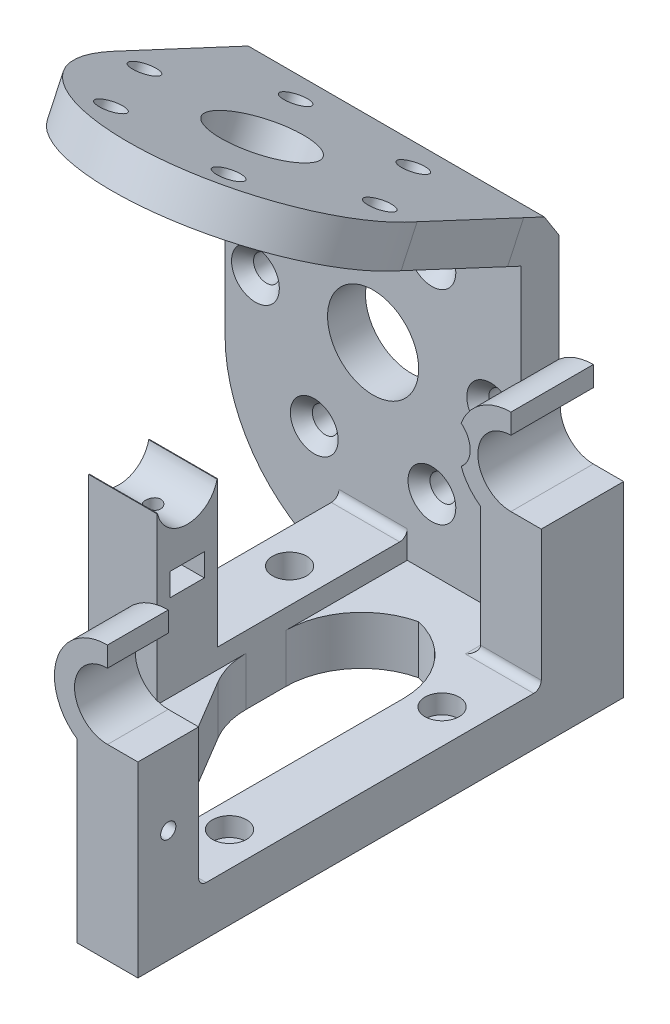
SolidWorks part; units mm, degrees
ref_plane "Front Plane" through (0, 0, 0) normal (0, 0, 1) x (1, 0, 0)
ref_plane "Top Plane" through (0, 0, 0) normal (0, 1, 0) x (1, 0, 0)
ref_plane "Right Plane" through (0, 0, 0) normal (1, 0, 0) x (0, 0, -1)
sketch "Sketch5" plane through (0, 0, 0) normal (0, 0, 1) x (1, 0, 0)
  line L0 (0, 0) -> (0, 15.5) construction
  circle A0 centre (0, 0) radius 19.5
  circle A1 centre (-7.75, 13.4234) radius 1.5
  circle A2 centre (0, 0) radius 6
  circle A3 centre (7.75, 13.4234) radius 1.5
  circle A4 centre (15.5, 0) radius 1.5
  circle A5 centre (7.75, -13.4234) radius 1.5
  circle A6 centre (-7.75, -13.4234) radius 1.5
  circle A7 centre (-15.5, 0) radius 1.5
  point P18 (0, 0)
  dimension "D2" = 3
  dimension "D3" = 39
  dimension "D4" = 12
  dimension "D1" = 15.5
  dimension "D5" = 6
extrude "Boss-Extrude1" add sketch "Sketch5" along normal blind 5
hole_wizard "CSK for M3 Flat Head Machine Screw1" positions "Sketch7" profile "Sketch6" countersink size "M3" standard "ANSI Metric" end condition through all
sketch "Sketch7" plane through (0, 0, 5) normal (0, 0, 1) x (1, 0, 0)
  point P0 (-15.5, 0)
  point P3 (-7.75, 13.4234)
  point P6 (7.75, 13.4234)
  point P9 (15.5, 0)
  point P12 (7.75, -13.4234)
  point P15 (-7.75, -13.4234)
sketch "Sketch6" plane through (-15.5, 0, 5) normal (1, 0, 0) x (0, -1, 0)
  line L0 (0, 0) -> (0, 5)
  line L1 (0, 5) -> (1.7, 5)
  line L2 (1.7, 5) -> (1.7, 1.45)
  line L3 (1.7, 1.45) -> (3.15, 0)
  line L5 (3.15, 0) -> (0, 0)
  line L6 (-1.7, 1.45) -> (-3.15, 0) construction
  line L11 (0, -6.35) -> (0, 107.95) construction
  dimension "Thru Hole Dia." = 3.4
  dimension "Thru Hole Depth" = 5
  dimension "Near C'Sink Dia." = 6.3
  dimension "Near C'Sink Angle" = 90
sketch "Sketch8" plane through (0, 0, 5) normal (0, 0, 1) x (1, 0, 0)
  line L0 (-19.5, 0) -> (-19.5, -25)
  line L1 (-19.5, -25) -> (19.5, -25)
  line L2 (19.5, -25) -> (19.5, 0)
  circle A0 centre (0, 0) radius 19.5 construction
  arc A1 (-19.5, 0) -> (19.5, 0) centre (0, 0) ccw
  dimension "D1" = 25
extrude "Boss-Extrude2" add sketch "Sketch8" against normal up to surface (5 mm away) up to face at (-13.8, 0, 0)
sketch "Sketch9" plane through (0, 0, 5) normal (0, 0, 1) x (1, 0, 0)
  line L0 (-19.5, -25) -> (19.5, -25) construction
  line L4 (-4.5, -20) -> (-4.5, -25)
  line L5 (4.5, -20) -> (-4.5, -25) construction
  line L6 (4.5, -25) -> (-4.5, -20) construction
  line L7 (-19.5, -25) -> (0, -22.5) construction
  line L8 (0, -22.5) -> (19.5, -25) construction
  line L9 (-4.5, -25) -> (4.5, -25)
  line L10 (-4.5, -20) -> (4.5, -20)
  line L11 (4.5, -20) -> (4.5, -25)
  point P0 (0, -22.5)
  dimension "D1" = 5
  dimension "D2" = 9
extrude "Boss-Extrude3" add sketch "Sketch9" along normal blind 32.9817
sketch "Sketch10" plane through (0.3712, -20, 0) normal (0, 1, 0) x (1, 0, 0)
  line L1 (-4.8712, -37.9817) -> (4.1288, -37.9817)
  line L2 (-4.8712, -37.9817) -> (-4.8712, -29.9817)
  line L3 (-4.8712, -29.9817) -> (4.1288, -29.9817)
  line L4 (4.1288, -37.9817) -> (4.1288, -29.9817)
  line L6 (-4.8712, -37.9817) -> (-4.8712, -5) construction
  line L7 (4.1288, -37.9817) -> (4.1288, -5) construction
  dimension "D1" = 8
extrude "Boss-Extrude4" add sketch "Sketch10" along normal blind 24
sketch "Sketch11" plane through (-4.5, 0, 0) normal (-1, 0, 0) x (0, 0, 1)
  line L0 (29.9817, 4) -> (29.9817, -20) construction
  line L2 (29.9817, 4) -> (37.9817, 4) construction
  line L3 (37.9817, 4) -> (37.9817, -25) construction
  line L4 (29.9817, 0) -> (27.1369, 2.0822)
  line L5 (27.1369, 2.0822) -> (27.3574, 4.8482)
  line L6 (27.3574, 4.8482) -> (32.7492, 5.4696)
  line L7 (32.7492, 5.4696) -> (41.4483, 5.0286)
  line L8 (41.4483, 5.0286) -> (40.8237, 2.383)
  line L9 (40.8237, 2.383) -> (37.9817, 0)
  line L10 (29.9817, -0.8) -> (30.0625, -0.8)
  line L11 (37.9009, -0.8) -> (37.9817, -0.8)
  line L12 (37.9817, 0) -> (37.9817, -0.8)
  line L13 (29.9817, -0.8) -> (29.9817, 0)
  arc A0 (30.0625, -0.8) -> (37.9009, -0.8) centre (33.9817, 0) ccw
  dimension "D1" = 0.8
extrude "Cut-Extrude1" cut sketch "Sketch11" against normal blind 20
sketch "Sketch12" plane through (0, -0.8, 0) normal (0, 1, 0) x (1, 0, 0)
  line L0 (-4.5, -29.9817) -> (4.5, -37.9817) construction
  line L1 (4.5, -29.9817) -> (-4.5, -37.9817) construction
  line L2 (4.5, -37.9009) -> (4.5, -30.0625) construction
  line L3 (4.5, -29.9817) -> (4.5, -5) construction
  circle A0 centre (0, -33.9817) radius 1
  dimension "D1" = 2
extrude "Cut-Extrude2" cut sketch "Sketch12" against normal blind 16
sketch "Sketch13" plane through (-4.5, 0, 0) normal (-1, 0, 0) x (0, 0, 1)
  line L0 (29.9817, -8.9707) -> (31.7317, -8.9707) construction
  line L1 (31.7317, -8.2443) -> (36.2317, -8.2443)
  line L2 (31.7317, -8.2443) -> (31.7317, -11.2443)
  line L3 (31.7317, -11.2443) -> (36.2317, -11.2443)
  line L4 (36.2317, -8.2443) -> (36.2317, -11.2443)
  line L5 (29.9817, -0.8) -> (29.9817, -20) construction
  line L6 (37.9817, -0.8) -> (37.9817, -25) construction
  line L7 (36.2317, -8.9707) -> (37.9817, -8.9707) construction
  dimension "D1" = 4.5
  dimension "D2" = 3
extrude "Cut-Extrude3" cut sketch "Sketch13" against normal up to surface (9 mm away) up to face at (4.5, -12.05, 26.7363)
sketch "Sketch14" plane through (0, -25, 0) normal (0, -1, 0) x (1, 0, 0)
  line L0 (4.5, 37.9817) -> (4.5, 5) construction
  line L1 (4.5, 5) -> (28.015, 5)
  line L2 (4.5, 5) -> (4.5, 11)
  line L3 (4.5, 11) -> (20.015, 11)
  line L4 (28.015, 5) -> (28.015, 12.4921)
  line L5 (28.015, 3.392) -> (28.015, 40.8737) construction
  line L6 (20.015, 100.392) -> (20.015, 53.8737) construction
  line L8 (28.015, 12.4921) -> (28.015, 64)
  line L9 (28.015, 64) -> (20.015, 64)
  line L10 (20.015, 11) -> (20.015, 64)
  line L12 (4.5, 5) -> (19.5, 5) construction
  dimension "D1" = 0
  dimension "D2" = 6
  dimension "D3" = 59
extrude "Boss-Extrude5" add sketch "Sketch14" against normal blind 2.4
sketch "Sketch15" plane through (28.015, 0, 0) normal (1, 0, 0) x (0, 0, -1)
  line L0 (-54.8737, 4) -> (-100.392, 4) construction
  line L1 (-64, -22.6) -> (-56, -22.6)
  line L2 (-64, -22.6) -> (-64, 4)
  line L3 (-64, 4) -> (-56, 4)
  line L4 (-56, -22.6) -> (-56, 4)
  line L6 (-5, -22.6) -> (-13, -22.6)
  line L7 (-5, -22.6) -> (-5, 4)
  line L8 (-5, 4) -> (-13, 4)
  line L9 (-13, -22.6) -> (-13, 4)
  dimension "D1" = 8
extrude "Boss-Extrude6" add sketch "Sketch15" against normal up to surface (8 mm away) up to face at (20.015, -23.8, 37.5)
sketch "Sketch16" plane through (0, 0, 64) normal (0, 0, 1) x (1, 0, 0)
  line L0 (20.015, -1.0579) -> (20.1574, -1.0579)
  line L1 (20.015, 4) -> (20.015, -25) construction
  line L2 (28.015, 4) -> (28.015, -25) construction
  line L3 (28.015, -1.0579) -> (30.9797, 0.9089)
  line L4 (30.9797, 0.9089) -> (30.0419, 7.8056)
  line L5 (20.015, -1.0579) -> (20.015, 9.2476)
  line L6 (20.015, 3) -> (20.015, 15.4952) construction
  line L7 (20.015, 9.2476) -> (30.0419, 7.8056)
  line L8 (27.8726, -1.0579) -> (28.015, -1.0579)
  arc A0 (20.1574, -1.0579) -> (27.8726, -1.0579) centre (24.015, 0) ccw
extrude "Cut-Extrude4" cut sketch "Sketch16" against normal up to surface (59 mm away) up to face at (22.51, -14.5333, 5)
sketch "Sketch17" plane through (0, -22.6, 0) normal (0, 1, 0) x (1, 0, 0)
  line L0 (20.015, -56) -> (20.015, -13) construction
  line L1 (20.015, -13.8581) -> (28.015, -13.8581)
  line L2 (20.015, -13.8581) -> (20.015, -10.8581)
  line L3 (20.015, -10.8581) -> (28.015, -10.8581)
  line L4 (28.015, -13.8581) -> (28.015, -10.8581)
  line L5 (28.015, -5) -> (28.015, -13) construction
  dimension "D1" = 3
extrude "Cut-Extrude5" cut sketch "Sketch17" along normal up to surface (21.5421 mm away) up to face at (20.0862, -1.0579, 9)
sketch "Sketch19" plane through (0, 0, 29.9817) normal (0, 0, -1) x (-1, 0, 0)
  circle A0 centre (-7.75, -13.4234) radius 3
  dimension "D1" = 6
extrude "Cut-Extrude6" [suppressed] cut sketch "Sketch19" against normal through all
sketch "Sketch20" plane through (0, -22.6, 0) normal (0, 1, 0) x (1, 0, 0)
  line L0 (20.015, -64) -> (4.5, -37.9817)
  line L1 (20.015, -55) -> (4.5, -28.9817)
  line L2 (20.015, -56) -> (20.015, -11) construction
  line L3 (4.5, -29.9817) -> (4.5, -5) construction
  line L4 (4.5, -28.9817) -> (4.5, -37.9817)
  line L5 (20.015, -55) -> (20.015, -64)
  dimension "D1" = 9
extrude "Boss-Extrude7" add sketch "Sketch20" against normal up to surface (2.4 mm away) up to face at (8.005, -25, 20.4969)
fillet "Fillet1" radius 10 3 edges at (20.015, -23.8, 11) (4.5, -23.8, 11) (4.5, -23.8, 28.9817)
fillet "Fillet2" radius 1 1 edges at (20.015, -23.8, 55)
fillet "Fillet3" radius 1 4 edges at (0, -20, 5) (20.015, -22.6, 7.9291) (24.015, -22.6, 10.8581) (24.015, -22.6, 56)
sketch "Sketch22" plane through (28.015, 0, 0) normal (1, 0, 0) x (0, 0, -1)
  circle A0 centre (-60, -7.7015) radius 1
extrude "Cut-Extrude7" [suppressed] cut sketch "Sketch22" against normal up to surface (8 mm away) up to face at (20.015, -11.329, 7.9291)
sketch "Sketch23" plane through (28.015, 0, 0) normal (1, 0, 0) x (0, 0, -1)
  circle A0 centre (-7.9291, -7.7015) radius 1
extrude "Cut-Extrude8" [suppressed] cut sketch "Sketch23" against normal up to surface (8 mm away) up to face at (20.015, -11.329, 7.9291)
sketch "Sketch24" plane through (0, 0, 5) normal (0, 0, -1) x (-1, 0, 0)
  line L0 (-20.015, -21.6) -> (-20.015, -1.0579) construction
  line L1 (-28.015, -1.0579) -> (-28.015, -25) construction
  line L4 (-20.015, -5.7446) -> (-20.015, -1.0579)
  line L5 (-28.015, -1.0579) -> (-28.015, -5.7446)
  line L6 (-27.8726, -1.0579) -> (-28.015, -1.0579)
  line L7 (-20.015, -1.0579) -> (-20.1574, -1.0579)
  arc A0 (-20.1574, -1.0579) -> (-27.8726, -1.0579) centre (-24.015, 0) ccw
  arc A1 (-20.015, -5.7446) -> (-17.4629, -2.4637) centre (-24.015, 0) ccw
  circle A2 centre (-15.5, 0) radius 3.15 construction
  arc A3 (-17.4629, 2.4637) -> (-17.4629, -2.4637) centre (-15.5, 0) ccw
  arc A4 (-17.4629, 2.4637) -> (-28.015, -5.7446) centre (-24.015, 0) ccw
  dimension "D1" = 14
extrude "Boss-Extrude8" add sketch "Sketch24" against normal up to surface (5.8581 mm away) up to face at (24.015, -8.3956, 10.8581)
sketch "Sketch25" plane through (0, 0, 64) normal (0, 0, 1) x (1, 0, 0)
  line L0 (20.015, -5.7446) -> (20.015, -1.0579)
  line L1 (20.015, -1.0579) -> (20.1574, -1.0579)
  line L2 (27.8726, -1.0579) -> (28.015, -1.0579)
  line L3 (28.015, -1.0579) -> (28.015, -5.7446)
  circle A0 centre (24.015, 0) radius 4 construction
  arc A2 (27.8726, -1.0579) -> (20.1574, -1.0579) centre (24.015, 0) ccw
  arc A3 (28.015, -5.7446) -> (20.015, -5.7446) centre (24.015, 0) ccw
extrude "Boss-Extrude9" add sketch "Sketch25" against normal up to surface (8 mm away) up to face at (24.015, -8.3956, 56)
sketch "Sketch26" plane through (0, 0, 64) normal (0, 0, 1) x (1, 0, 0)
  circle A0 centre (24.015, 0) radius 4.35
  dimension "D1" = 8.7
extrude "Cut-Extrude9" cut sketch "Sketch26" against normal up to surface (59 mm away) up to face at (22.1195, -11.2362, 5)
sketch "Sketch27" plane through (0, -25, 0) normal (0, -1, 0) x (1, 0, 0)
  line L0 (4.5, 26.2265) -> (4.5, 21) construction
  line L1 (20.015, 51.3705) -> (20.015, 21) construction
  line L2 (18.1561, 51.8827) -> (5.9111, 31.3481) construction
  line L3 (4.5, 26.2265) -> (4.5, 21)
  line L4 (20.015, 51.3705) -> (20.015, 21)
  line L5 (18.1561, 51.8827) -> (5.9111, 31.3481)
  line L10 (19.5, 0) -> (19.5, 5)
  line L11 (19.5, 5) -> (28.015, 5)
  line L12 (28.015, 5) -> (28.015, 64)
  line L13 (28.015, 64) -> (20.015, 64)
  line L14 (20.015, 64) -> (4.5, 37.9817)
  line L15 (4.5, 37.9817) -> (-4.5, 37.9817)
  line L16 (-4.5, 37.9817) -> (-4.5, 5)
  line L17 (-4.5, 5) -> (-19.5, 5)
  line L18 (-19.5, 5) -> (-19.5, 0)
  line L19 (-19.5, 0) -> (19.5, 0)
  line L20 (19.5, 0) -> (19.5, 5)
  line L21 (19.5, 5) -> (28.015, 5)
  line L22 (28.015, 5) -> (28.015, 64)
  line L23 (28.015, 64) -> (20.015, 64)
  line L24 (20.015, 64) -> (4.5, 37.9817)
  line L25 (4.5, 37.9817) -> (-4.5, 37.9817)
  line L26 (-4.5, 37.9817) -> (-4.5, 5)
  line L27 (-4.5, 5) -> (-19.5, 5)
  line L28 (-19.5, 5) -> (-19.5, 0)
  line L29 (-19.5, 0) -> (19.5, 0)
  arc A0 (12.2575, 11.2547) -> (20.015, 21) centre (10.015, 21) ccw construction
  arc A1 (4.5, 21) -> (12.2575, 11.2547) centre (14.5, 21) ccw construction
  arc A2 (5.9111, 31.3481) -> (4.5, 26.2265) centre (14.5, 26.2265) ccw construction
  arc A3 (20.015, 51.3705) -> (18.1561, 51.8827) centre (19.015, 51.3705) ccw construction
  arc A4 (12.2575, 11.2547) -> (20.015, 21) centre (10.015, 21) ccw
  arc A5 (4.5, 21) -> (12.2575, 11.2547) centre (14.5, 21) ccw
  arc A6 (5.9111, 31.3481) -> (4.5, 26.2265) centre (14.5, 26.2265) ccw
  arc A7 (20.015, 51.3705) -> (18.1561, 51.8827) centre (19.015, 51.3705) ccw
  dimension "D1" = 0
extrude "Boss-Extrude10" add sketch "Sketch27" along normal blind 4
sketch "Sketch28" plane through (0, -22.6, 0) normal (0, 1, 0) x (1, 0, 0)
  line L0 (23.515, -11.8581) -> (23.515, -55) construction
  line L3 (23.515, -19.4291) -> (23.515, -33.4291) construction
  line L4 (23.515, -33.4291) -> (23.515, -47.4291) construction
  circle A0 centre (23.515, -19.4291) radius 1
  circle A1 centre (23.515, -47.4291) radius 1
  dimension "D1" = 2
  dimension "D2" = 28
  dimension "D3" = 14
extrude "Cut-Extrude10" cut sketch "Sketch28" against normal through all
sketch "Sketch29" plane through (0, -22.6, 0) normal (0, 1, 0) x (1, 0, 0)
  circle A0 centre (23.515, -19.4291) radius 2.25
  circle A1 centre (23.515, -47.4291) radius 2.25
  dimension "D1" = 4.5
extrude "Cut-Extrude11" cut sketch "Sketch29" against normal blind 2.5
sketch "Sketch30" plane through (0, -20, 0) normal (0, 1, 0) x (1, 0, 0)
  line L0 (4.5, -6) -> (-4.5, -6) construction
  circle A0 centre (0, -16) radius 1
  dimension "D1" = 2
  dimension "D2" = 10
extrude "Cut-Extrude12" cut sketch "Sketch30" against normal through all
sketch "Sketch31" plane through (0, -20, 0) normal (0, 1, 0) x (1, 0, 0)
  circle A0 centre (0, -16) radius 2.25
  dimension "D1" = 4.5
extrude "Cut-Extrude13" cut sketch "Sketch31" against normal blind 5
ref_axis "Axis1" through (35.3555, 0, 33.9817) along (-1, 0, 0)
pattern_circular "CirPattern1" count 2 every 65 about axis through (35.3555, 0, 33.9817) along (-1, 0, 0) of "Boss-Extrude1", "CSK for M3 Flat Head Machine Screw1" reverse direction yes
sketch "Sketch32" plane through (0, 0, 0) normal (0, 0, -1) x (-1, 0, 0)
  line L1 (-19.5, 0) -> (-19.5, -29) construction
  line L2 (-19.5, -29) -> (-28.015, -29) construction
  line L3 (-28.015, -5.7446) -> (-28.015, -29) construction
  line L4 (-19.5, 0) -> (-19.5, -29)
  line L7 (-19.5, -29) -> (-28.015, -29)
  line L15 (-28.015, -5.7446) -> (-28.015, -29)
  arc A0 (-18.9042, 4.7833) -> (-19.5, 0) centre (0, 0) ccw construction
  arc A1 (-18.9042, 4.7833) -> (-28.015, -5.7446) centre (-24.015, 0) ccw construction
  arc A2 (-18.9042, 4.7833) -> (-19.5, 0) centre (0, 0) ccw
  arc A3 (-18.9042, 4.7833) -> (-28.015, -5.7446) centre (-24.015, 0) ccw
  circle A12 centre (-24.015, 0) radius 4.35 construction
  circle A13 centre (-24.015, 0) radius 4.35
extrude "Boss-Extrude11" add sketch "Sketch32" against normal up to surface (5 mm away) up to face at (19.665, 0, 5)
sketch "Sketch33" plane through (0, 0, 0) normal (0, 0, -1) x (-1, 0, 0)
  line L0 (-24.015, 0) -> (-24.015, 7)
  line L1 (-24.015, 0) -> (-24.015, -4.35)
  line L2 (-24.015, -4.35) -> (-32.4433, -4.35)
  line L3 (-32.4433, -4.35) -> (-32.4433, 7)
  line L4 (-32.4433, 7) -> (-24.015, 7)
  arc A0 (-18.9042, 4.7833) -> (-28.015, -5.7446) centre (-24.015, 0) ccw construction
  circle A1 centre (-24.015, 0) radius 4.35 construction
extrude "Cut-Extrude14" cut sketch "Sketch33" against normal up to surface (64 mm away) up to face at (28.365, 0, 64)
fillet "Fillet5" radius 20 1 edges at (-19.5, -29, 2.5)
sketch "Sketch34" plane through (-19.5, 0, 0) normal (-1, 0, 0) x (0, 0, 1)
  line L0 (1.9474, 22.5568) -> (0, 19.5)
  line L1 (0, 19.5) -> (0, 16.5)
  line L2 (0, 19.5) -> (0, 0) construction
  line L3 (0, 16.5) -> (5, 16.5)
  line L4 (5, 0) -> (5, 18.4634) construction
  line L5 (5, 16.5) -> (5, 18.4634)
  line L6 (5, 18.4634) -> (6.7794, 19.2931)
  line L7 (5, 18.4634) -> (39.4065, 34.5074) construction
  line L8 (6.7794, 19.2931) -> (4.6663, 23.8246)
  line L9 (8.9954, 25.8433) -> (5.9139, 24.4064) construction
  line L10 (4.6663, 23.8246) -> (1.9474, 22.5568)
  dimension "D1" = 3
extrude "Boss-Extrude12" add sketch "Sketch34" against normal blind 39
sketch "Sketch35" plane through (0, 0, 0) normal (0, 0, -1) x (-1, 0, 0)
  line L0 (19.5, 16.5) -> (19.5, 0)
  line L1 (19.5, 16.5) -> (10.3923, 16.5)
  line L2 (-19.5, 16.5) -> (-19.5, 5.3493)
  line L3 (-19.5, 16.5) -> (-10.3923, 16.5)
  arc A0 (19.5, 0) -> (10.3923, 16.5) centre (0, 0) ccw construction
  arc A1 (19.5, 0) -> (10.3923, 16.5) centre (0, 0) ccw
  arc A2 (-18.9042, 4.7833) -> (-24.015, 7) centre (-24.015, 0) ccw construction
  arc A3 (-10.3923, 16.5) -> (-18.9042, 4.7833) centre (0, 0) ccw construction
  arc A4 (-10.3923, 16.5) -> (-18.9042, 4.7833) centre (0, 0) ccw
  arc A5 (-18.9042, 4.7833) -> (-19.5, 5.3493) centre (-24.015, 0) ccw
extrude "Boss-Extrude13" add sketch "Sketch35" against normal up to surface (5 mm away) up to face at (-7.75, 13.3867, 5)
sketch "Sketch36" plane through (0, 17.7821, -8.2919) normal (0, 0.9063, -0.4226) x (1, 0, 0)
  line L0 (-19.5, -14.2979) -> (-19.5, -30.7979)
  line L1 (-19.5, -14.2979) -> (-10.3923, -14.2979)
  line L2 (10.3923, -14.2979) -> (19.5, -14.2979)
  line L3 (19.5, -14.2979) -> (19.4713, -29.7411)
  arc A0 (-10.3923, -14.2979) -> (10.3923, -14.2979) centre (0, -30.7979) ccw construction
  arc A1 (-10.3923, -14.2979) -> (-19.5, -30.7979) centre (0, -30.7979) ccw
  arc A2 (19.4713, -29.7411) -> (10.3923, -14.2979) centre (0, -30.7979) ccw
extrude "Boss-Extrude14" add sketch "Sketch36" against normal up to surface (5 mm away) up to face at (7.75, 20.6088, 9.601)
sketch "Sketch37" plane through (0, -29, 0) normal (0, -1, 0) x (-1, 0, 0)
  line L1 (-28.015, -64) -> (-52.5711, -64)
  line L2 (-28.015, -64) -> (-28.015, 2.139)
  line L3 (-28.015, 2.139) -> (-52.5711, 2.139)
  line L4 (-52.5711, -64) -> (-52.5711, 2.139)
extrude "Cut-Extrude15" cut sketch "Sketch37" against normal up to surface (24.65 mm away) up to face at (26.7571, -4.35, 60)
sketch "Sketch38" plane through (28.015, 0, 0) normal (1, 0, 0) x (0, 0, -1)
  circle A0 centre (-60, -14.1723) radius 1
extrude "Cut-Extrude16" cut sketch "Sketch38" against normal blind 31
